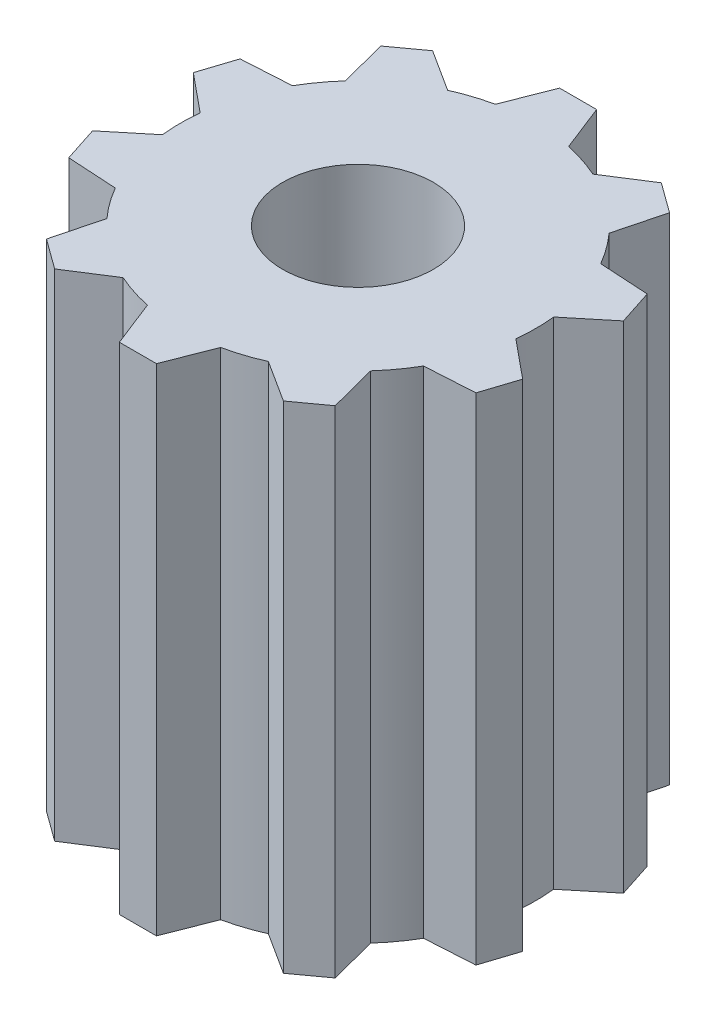
SolidWorks part; units mm, degrees
ref_plane "Front Plane" through (0, 0, 0) normal (0, 0, 1) x (1, 0, 0)
ref_plane "Top Plane" through (0, 0, 0) normal (0, 1, 0) x (1, 0, 0)
ref_plane "Right Plane" through (0, 0, 0) normal (1, 0, 0) x (0, 0, -1)
sketch "Sketch1" plane through (0, 0, 0) normal (0, 1, 0) x (1, 0, 0)
  circle A0 centre (0, 0) radius 3.5
extrude "Boss-Extrude1" add sketch "Sketch1" along normal blind 5
sketch "Sketch2" plane through (0, 5, 0) normal (0, 1, 0) x (1, 0, 0)
  circle A0 centre (0, 0) radius 3.5
ref_plane "Plane2" through (0, 5, 0) normal (0, -1, 0) x (-1, 0, 0)
sketch "Sketch12" plane through (0, 5, 0) normal (0, -1, 0) x (-1, 0, 0)
  circle A0 centre (0, 0) radius 3.5 construction
  circle A2 centre (0, 0) radius 12.25 construction
  circle A3 centre (0, 0) radius 8.25
  circle A4 centre (0, 0) radius 10.25 construction
  circle A5 centre (0, 0) radius 3.5
  dimension "D1" = 16.5
  dimension "D2" = 20.5
  dimension "D3" = 24.5
extrude "Boss-Extrude6" add sketch "Sketch12" along normal blind 5 separate body
sketch "Sketch13" plane through (0, 0, 0) normal (0, -1, 0) x (1, 0, 0)
  line L0 (0, 12.25) -> (0, -12.25) construction
  line L1 (-12.25, 0) -> (12.25, 0) construction
  line L2 (0.86, 10.2139) -> (1.7, 8.0729)
  line L3 (-0.86, 10.2139) -> (-1.7, 8.0729)
  line L4 (-0.86, 10.2139) -> (0.86, 10.2139)
  line L5 (-1.7, 8.0729) -> (3.0326, 8.2556) construction
  circle A0 centre (0, 0) radius 10.25 construction
  circle A1 centre (0, 0) radius 12.25 construction
  circle A3 centre (0, 0) radius 8.25 construction
  circle A4 centre (0, 0) radius 8.25
  circle A5 centre (0, 0) radius 8.25
  circle A6 centre (0, 0) radius 8.25
  point P11 (0, 0)
  circle M1 centre (0, 0) radius 8.25
  dimension "D1" = 20.5
  dimension "D2" = 24.5
  dimension "D3" = 16.5
  dimension "D4" = 1.7
  dimension "D5" = 1.7
  dimension "D6" = 1.72
  dimension "D7" = 66.367
  dimension "D8" = 0
extrude "Boss-Extrude9" add sketch "Sketch13" against normal blind 5 separate body contours L4 L3 L2 M1 region at (0, 0, 9.0962)
pattern_circular "CirPattern2" count 10 over 360 about axis through (0, 0, 0) along (0, -1, 0) of bodies 130
sketch "Sketch14" plane through (0, 5, 0) normal (0, 1, 0) x (1, 0, 0)
  circle A0 centre (0, 0) radius 3.5 construction
  circle A1 centre (0, 0) radius 3.5
extrude "Cut-Extrude1" cut sketch "Sketch14" against normal blind 10
sketch "Sketch17" plane through (0, 0, 0) normal (0, -1, 0) x (1, 0, 0)
  line L0 (9.4482, -3.9742) -> (9.9797, -2.3383) construction
  line L1 (9.9797, -2.3383) -> (8.2032, -0.8779) construction
  line L2 (7.1525, -4.1115) -> (9.4482, -3.9742) construction
  line L3 (5.3078, -8.7687) -> (6.6993, -7.7577) construction
  line L4 (6.6993, -7.7577) -> (6.1205, -5.5319) construction
  line L5 (3.3698, -7.5304) -> (5.3078, -8.7687) construction
  line L6 (-0.86, -10.2139) -> (0.86, -10.2139) construction
  line L7 (0.86, -10.2139) -> (1.7, -8.0729) construction
  line L8 (-1.7, -8.0729) -> (-0.86, -10.2139) construction
  line L9 (-6.6993, -7.7577) -> (-5.3078, -8.7687) construction
  line L10 (-5.3078, -8.7687) -> (-3.3698, -7.5304) construction
  line L11 (-6.1205, -5.5319) -> (-6.6993, -7.7577) construction
  line L12 (-9.9797, -2.3383) -> (-9.4482, -3.9742) construction
  line L13 (-9.4482, -3.9742) -> (-7.1525, -4.1115) construction
  line L14 (-8.2032, -0.8779) -> (-9.9797, -2.3383) construction
  line L15 (-5.3078, 8.7687) -> (-6.6993, 7.7577) construction
  line L16 (-6.6993, 7.7577) -> (-6.1205, 5.5319) construction
  line L17 (-3.3698, 7.5304) -> (-5.3078, 8.7687) construction
  line L18 (-9.4482, 3.9742) -> (-9.9797, 2.3383) construction
  line L19 (-9.9797, 2.3383) -> (-8.2032, 0.8779) construction
  line L20 (-7.1525, 4.1115) -> (-9.4482, 3.9742) construction
  line L21 (9.9797, 2.3383) -> (9.4482, 3.9742) construction
  line L22 (9.4482, 3.9742) -> (7.1525, 4.1115) construction
  line L23 (8.2032, 0.8779) -> (9.9797, 2.3383) construction
  line L24 (6.6993, 7.7577) -> (5.3078, 8.7687) construction
  line L25 (5.3078, 8.7687) -> (3.3698, 7.5304) construction
  line L26 (6.1205, 5.5319) -> (6.6993, 7.7577) construction
  line L27 (0.86, 10.2139) -> (-0.86, 10.2139) construction
  line L28 (-0.86, 10.2139) -> (-1.7, 8.0729) construction
  line L29 (1.7, 8.0729) -> (0.86, 10.2139) construction
  line L30 (9.4482, -3.9742) -> (9.9797, -2.3383)
  line L31 (9.9797, -2.3383) -> (8.2032, -0.8779)
  line L32 (7.1525, -4.1115) -> (9.4482, -3.9742)
  line L33 (5.3078, -8.7687) -> (6.6993, -7.7577)
  line L34 (6.6993, -7.7577) -> (6.1205, -5.5319)
  line L35 (3.3698, -7.5304) -> (5.3078, -8.7687)
  line L36 (-0.86, -10.2139) -> (0.86, -10.2139)
  line L37 (0.86, -10.2139) -> (1.7, -8.0729)
  line L38 (-1.7, -8.0729) -> (-0.86, -10.2139)
  line L39 (-6.6993, -7.7577) -> (-5.3078, -8.7687)
  line L40 (-5.3078, -8.7687) -> (-3.3698, -7.5304)
  line L41 (-6.1205, -5.5319) -> (-6.6993, -7.7577)
  line L42 (-9.9797, -2.3383) -> (-9.4482, -3.9742)
  line L43 (-9.4482, -3.9742) -> (-7.1525, -4.1115)
  line L44 (-8.2032, -0.8779) -> (-9.9797, -2.3383)
  line L45 (-5.3078, 8.7687) -> (-6.6993, 7.7577)
  line L46 (-6.6993, 7.7577) -> (-6.1205, 5.5319)
  line L47 (-3.3698, 7.5304) -> (-5.3078, 8.7687)
  line L48 (-9.4482, 3.9742) -> (-9.9797, 2.3383)
  line L49 (-9.9797, 2.3383) -> (-8.2032, 0.8779)
  line L50 (-7.1525, 4.1115) -> (-9.4482, 3.9742)
  line L51 (9.9797, 2.3383) -> (9.4482, 3.9742)
  line L52 (9.4482, 3.9742) -> (7.1525, 4.1115)
  line L53 (8.2032, 0.8779) -> (9.9797, 2.3383)
  line L54 (6.6993, 7.7577) -> (5.3078, 8.7687)
  line L55 (5.3078, 8.7687) -> (3.3698, 7.5304)
  line L56 (6.1205, 5.5319) -> (6.6993, 7.7577)
  line L57 (0.86, 10.2139) -> (-0.86, 10.2139)
  line L58 (-0.86, 10.2139) -> (-1.7, 8.0729)
  line L59 (1.7, 8.0729) -> (0.86, 10.2139)
  arc A0 (7.1525, -4.1115) -> (8.2032, -0.8779) centre (0, 0) ccw construction
  arc A1 (3.3698, -7.5304) -> (6.1205, -5.5319) centre (0, 0) ccw construction
  arc A2 (-1.7, -8.0729) -> (1.7, -8.0729) centre (0, 0) ccw construction
  arc A4 (-6.1205, -5.5319) -> (-3.3698, -7.5304) centre (0, 0) ccw construction
  arc A5 (-8.2032, -0.8779) -> (-7.1525, -4.1115) centre (0, 0) ccw construction
  arc A6 (-3.3698, 7.5304) -> (-6.1205, 5.5319) centre (0, 0) ccw construction
  arc A7 (-7.1525, 4.1115) -> (-8.2032, 0.8779) centre (0, 0) ccw construction
  arc A8 (8.2032, 0.8779) -> (7.1525, 4.1115) centre (0, 0) ccw construction
  arc A9 (6.1205, 5.5319) -> (3.3698, 7.5304) centre (0, 0) ccw construction
  arc A10 (1.7, 8.0729) -> (-1.7, 8.0729) centre (0, 0) ccw construction
  circle A11 centre (0, 0) radius 8.25 construction
  arc A12 (7.1525, -4.1115) -> (8.2032, -0.8779) centre (0, 0) ccw
  arc A13 (3.3698, -7.5304) -> (6.1205, -5.5319) centre (0, 0) ccw
  arc A14 (-1.7, -8.0729) -> (1.7, -8.0729) centre (0, 0) ccw
  arc A15 (-6.1205, -5.5319) -> (-3.3698, -7.5304) centre (0, 0) ccw
  arc A16 (-8.2032, -0.8779) -> (-7.1525, -4.1115) centre (0, 0) ccw
  arc A17 (-3.3698, 7.5304) -> (-6.1205, 5.5319) centre (0, 0) ccw
  arc A18 (-7.1525, 4.1115) -> (-8.2032, 0.8779) centre (0, 0) ccw
  arc A19 (8.2032, 0.8779) -> (7.1525, 4.1115) centre (0, 0) ccw
  arc A20 (6.1205, 5.5319) -> (3.3698, 7.5304) centre (0, 0) ccw
  arc A21 (1.7, 8.0729) -> (-1.7, 8.0729) centre (0, 0) ccw
  circle A22 centre (0, 0) radius 8.25
  circle M1 centre (0, 0) radius 8.25
  circle M2 centre (0, 0) radius 3.5
other "AlignGroup1"
other "AlignGroup2"
extrude "Boss-Extrude10" add sketch "Sketch17" along normal blind 18 contours M1 M2 | L59 L57 L58 M1 | L47 L45 L46 M1 | L50 L48 L49 M1 | L44 L42 L43 M1 | L41 L39 L40 M1 | L38 L36 L37 M1 | L35 L33 L34 M1 | L32 L30 L31 M1 | L53 L51 L52 M1 | L56 L54 L55 M1 region at (8.651, 0, -2.8109) region at (6.4856, 0, -4.7121) region at (5.3466, 0, -7.359) region at (8.651, 0, 2.8109) region at (0, 0, -9.0962) region at (5.3466, 0, 7.359) region at (-5.3466, 0, -7.359) region at (0, 0, 9.0962) region at (-8.651, 0, -2.8109) region at (-5.3466, 0, 7.359) region at (-8.651, 0, 2.8109)
